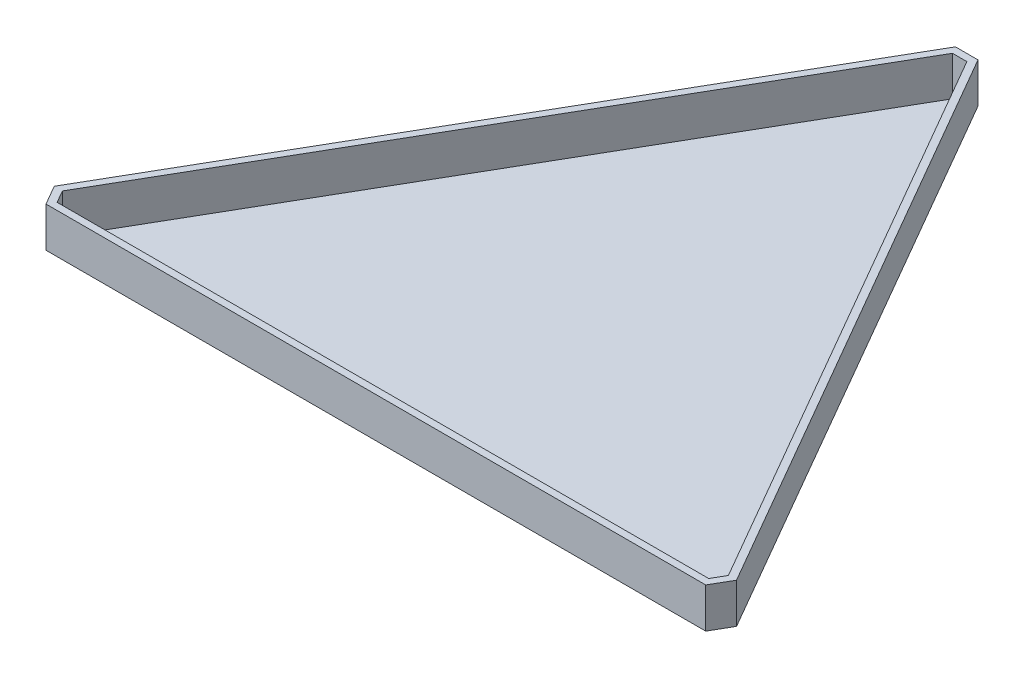
SolidWorks part; units mm, degrees
ref_plane "Front Plane" through (0, 0, 0) normal (0, 0, 1) x (1, 0, 0)
ref_plane "Top Plane" through (0, 0, 0) normal (0, 1, 0) x (1, 0, 0)
ref_plane "Right Plane" through (0, 0, 0) normal (1, 0, 0) x (0, 0, -1)
sketch "Sketch1" plane through (0, 0, 0) normal (0, 1, 0) x (1, 0, 0)
  line L0 (351.2729, 67.6655) -> (468.273, -134.9846)
  line L1 (347.2728, 67.6655) -> (347.2728, 65.1655) construction
  line L2 (409.773, -33.6595) -> (407.6079, -34.9095) construction
  line L3 (468.273, -134.9846) -> (464.2732, -141.9124)
  line L4 (230.2733, -141.9124) -> (464.2732, -141.9124)
  line L5 (230.2733, -141.9124) -> (226.2727, -134.9842)
  line L6 (226.2727, -134.9842) -> (343.2728, 67.6655)
  line L7 (353.4142, 63.9567) -> (351.2491, 62.7067) construction
  line L8 (347.2733, -141.9124) -> (347.2733, -139.4124) construction
  line L9 (231.7167, -139.4124) -> (462.8299, -139.4124)
  line L10 (284.7727, -33.6594) -> (286.9378, -34.9094) construction
  line L11 (344.7161, 65.1655) -> (349.8295, 65.1655)
  line L12 (465.3862, -134.9846) -> (349.8295, 65.1655)
  line L13 (466.2731, -138.4485) -> (464.1081, -137.1985) construction
  line L14 (462.8299, -139.4124) -> (465.3862, -134.9846)
  line L15 (229.1594, -134.9842) -> (344.7161, 65.1655)
  line L16 (229.1594, -134.9842) -> (231.7167, -139.4124)
  line L20 (343.2728, 67.6655) -> (351.2729, 67.6655)
  point P13 (407.6079, -34.9095)
  point P20 (464.1081, -137.1985)
  point P23 (347.2733, -139.4124)
  point P25 (347.2732, -141.9124)
  point P27 (347.2728, 65.1655)
  point P31 (286.9378, -34.9094)
  dimension "D1" = 2.5
  dimension "D2" = 2.5
  dimension "D3" = 2.5
  dimension "D4" = 2.5
  dimension "D5" = 2.5
  dimension "D6" = 2.5
extrude "Boss-Extrude6" add sketch "Sketch1" along normal blind 0.2 contours L16 L9 L14 L12 L11 L15
extrude "Boss-Extrude8" add sketch "Sketch1<7>" along normal blind 14.2
sketch "Sketch1<7>" plane through (0, 0, 0) normal (0, 1, 0) x (1, 0, 0) same geometry as "Sketch1"
